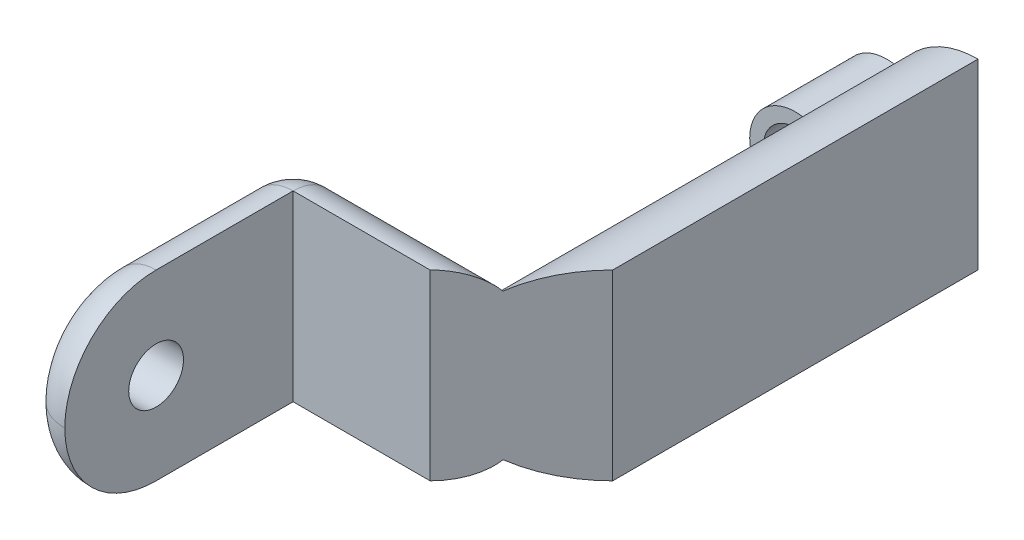
SolidWorks part; units mm, degrees
ref_plane "Alzado" through (0, 0, 0) normal (0, 0, 1) x (1, 0, 0)
ref_plane "Planta" through (0, 0, 0) normal (0, 1, 0) x (1, 0, 0)
ref_plane "Vista lateral" through (0, 0, 0) normal (1, 0, 0) x (0, 0, -1)
sketch "Croquis1" plane through (0, 0, 0) normal (0, 0, 1) x (1, 0, 0)
  circle A0 centre (0, 0) radius 3.5
  circle A1 centre (0, 0) radius 5
  dimension "D1" = 10
  dimension "D2" = 7
extrude "Saliente-Extruir1" add sketch "Croquis1" along normal blind 5 and the other way blind 5
sketch "Croquis2" plane through (0, 0, 0) normal (0, 0, 1) x (1, 0, 0)
  line L0 (5, 0) -> (15, 0) construction
  line L1 (10, -10) -> (10, 10)
  arc A0 (10, 10) -> (10, -10) centre (10, 0) ccw
  circle A1 centre (0, 0) radius 5 construction
  dimension "D2" = 20
  dimension "D3" = 10
  dimension "D1" = 10
extrude "Saliente-Extruir2" add sketch "Croquis2" along normal blind 40 and the other way blind 5
sketch "Croquis3" plane through (10, 0, 0) normal (1, 0, 0) x (0, 0, -1)
  line L0 (-40, 0) -> (-35, 0) construction
  line L1 (-40, -10) -> (-40, 10) construction
  line L2 (-40, 0) -> (-40, 7) construction
  line L3 (-40, 10) -> (-40, -10)
  line L4 (-35, -10) -> (-45, -10)
  line L5 (-35, -10) -> (-35, 10)
  line L6 (-35, 10) -> (-45, 10)
  line L7 (-45, -10) -> (-45, 10)
  line L8 (-35, -10) -> (-45, 10) construction
  line L9 (-35, 10) -> (-45, -10) construction
  line M2 (-40, 10) -> (-40, -10)
  dimension "D1" = 5
  dimension "D2" = 7
  dimension "D3" = 10
  dimension "D4" = 20
sketch "Croquis7" plane through (0, 0, 0) normal (0, 0, 1) x (1, 0, 0)
  circle A0 centre (0, 0) radius 3.5
extrude "Cortar-Extruir1" cut sketch "Croquis7" against normal blind 5 and the other way blind 5
extrude "Saliente-Extruir3" add sketch "Croquis3" against normal blind 30 contours L7 L4 L6 M2 region at (10, 0, 42.5)
sketch "Croquis9" plane through (0, 0, 45) normal (0, 0, 1) x (1, 0, 0)
  line L1 (-15, 0) -> (-17.5, 0) construction
  line L3 (-15, -10) -> (-20, -10)
  line L4 (-15, -10) -> (-15, 10)
  line L5 (-15, 10) -> (-20, 10)
  line L6 (-20, -10) -> (-20, 10)
  line L7 (-15, -10) -> (-20, 10) construction
  line L8 (-15, 10) -> (-20, -10) construction
  dimension "D2" = 2.5
  dimension "D3" = 5
  dimension "D4" = 20
extrude "Saliente-Extruir4" add sketch "Croquis9" along normal blind 25
sketch "Croquis11" plane through (-20, 0, 0) normal (-1, 0, 0) x (0, 0, 1)
  line L0 (70, 0) -> (60, 0) construction
  line L1 (70, 10) -> (70, -10) construction
  circle A0 centre (60, 0) radius 3
  dimension "D2" = 6
  dimension "D1" = 10
extrude "Cortar-Extruir3" cut sketch "Croquis11" against normal blind 6
fillet "Redondeo5" radius 10 2 edges at (-17.5, -10, 70) (-17.5, 10, 70)
fillet "Redondeo7" radius 5 4 edges at (-20, -10, 50) (-20, -7.0711, 67.0711) (-20, 7.0711, 67.0711) (-20, 10, 50)
fillet "Redondeo8" radius 5 5 edges at (-2.5, 10, 40) (-18.5355, 8.5355, 40) (-2.5, -10, 40) (-18.5355, -8.5355, 40) (-20, 0, 40)
sketch "Croquis12" plane through (0, 0, 5) normal (0, 0, 1) x (1, 0, 0)
  circle A0 centre (0, 0) radius 5
extrude "Cortar-Extruir4" cut sketch "Croquis12" along normal blind 35
chamfer "Chaflán1" distance 10 angle 45 1 edges at (10, 0, 45)
